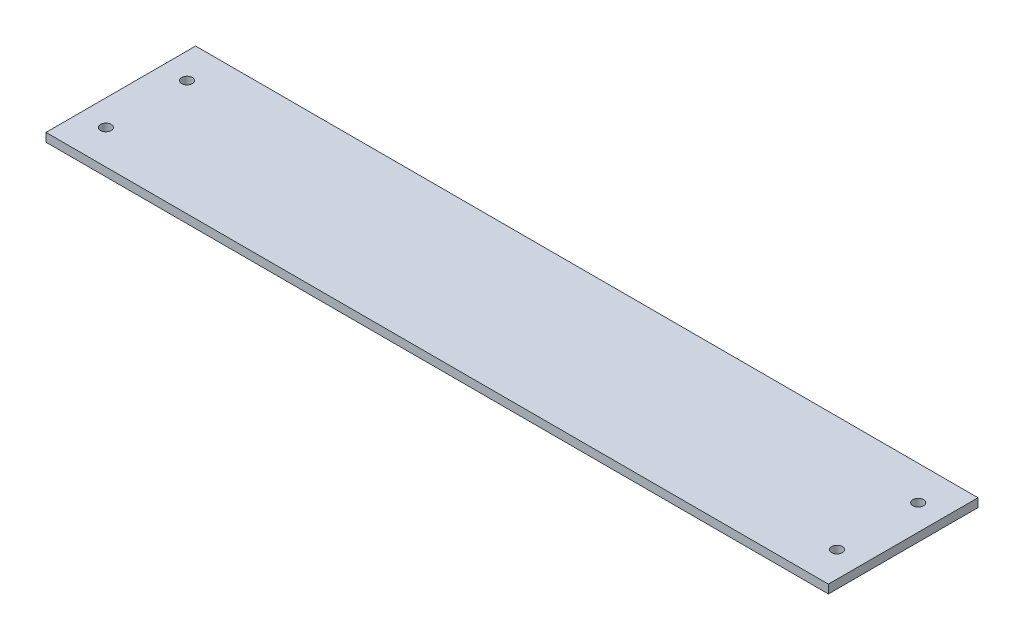
SolidWorks part; units mm, degrees
ref_plane "Front Plane" through (0, 0, 0) normal (0, 0, 1) x (1, 0, 0)
ref_plane "Top Plane" through (0, 0, 0) normal (0, 1, 0) x (1, 0, 0)
ref_plane "Right Plane" through (0, 0, 0) normal (1, 0, 0) x (0, 0, -1)
sketch "Sketch1" plane through (0, 0, 0) normal (0, 1, 0) x (1, 0, 0)
  line L1 (-91.52, 17.5) -> (91.52, 17.5)
  line L2 (-91.52, 17.5) -> (-91.52, -17.5)
  line L3 (-91.52, -17.5) -> (91.52, -17.5)
  line L4 (91.52, 17.5) -> (91.52, -17.5)
  line L5 (-91.52, 17.5) -> (91.52, -17.5) construction
  line L6 (-91.52, -17.5) -> (91.52, 17.5) construction
  point P0 (0, 0)
  dimension "D1" = 35
  dimension "D2" = 183.04
base flange "Base-Flange1" sketch "Sketch1" thickness 2 reverse thickness direction no parameters "D1"=2
hole_wizard "Tap Drill for M3 Tap1" positions "Sketch2" profile "Sketch3" hole size "M3" standard "AS" end condition through all
sketch "Sketch2" plane through (-65.8659, 2, 15.8304) normal (0, 1, 0) x (0, 0, -1)
  point P0 (25.3304, 19.6541)
  point P2 (6.3304, 19.6541)
  point P11 (0, 0)
sketch "Sketch3" plane through (-85.52, 2, -9.5) normal (1, 0, 0) x (0, 0, 1)
  line L0 (0, 0) -> (0, 4)
  line L1 (0, 4) -> (1.25, 4)
  line L2 (1.25, 4) -> (1.25, 0)
  line L3 (1.25, 0) -> (0, 0)
  line L4 (0, -6.35) -> (0, 107.95) construction
  dimension "Thru Hole Dia." = 2.5
  dimension "Thru Hole Depth" = 4
hole_wizard "Tap Drill for M3 Tap2" positions "Sketch4" profile "Sketch5" hole size "M3" standard "AS" end condition through all
sketch "Sketch4" plane through (-65.8659, 2, 15.8304) normal (0, 1, 0) x (0, 0, -1)
  point P0 (25.3304, -151.4044)
  point P2 (6.3304, -151.4044)
  point P11 (0, 0)
sketch "Sketch5" plane through (85.5385, 2, -9.5) normal (1, 0, 0) x (0, 0, 1)
  line L0 (0, 0) -> (0, 4)
  line L1 (0, 4) -> (1.25, 4)
  line L2 (1.25, 4) -> (1.25, 0)
  line L3 (1.25, 0) -> (0, 0)
  line L4 (0, -6.35) -> (0, 107.95) construction
  dimension "Thru Hole Dia." = 2.5
  dimension "Thru Hole Depth" = 4
sketch "Bend-Lines1" [suppressed] plane through (0, 0, 0) normal (0, 1, 0) x (1, 0, 0)
sketch "Bounding-Box1" [suppressed] plane through (0, 0, 0) normal (0, 1, 0) x (1, 0, 0)
sheet metal parameters "Sheet-Metal1" thickness 2 parameters "D1"=2
flat pattern "Flat-Pattern1" [suppressed]
sketch "Bend-Lines2" plane through (0, 0, 0) normal (0, 1, 0) x (1, 0, 0)
sketch3d "Bounding-Box2" [suppressed]
  line L0 (91.52, -17.5, 0) -> (-91.52, -17.5, 0) construction
  line L1 (91.52, 17.5, 0) -> (-91.52, 17.5, 0) construction
  line L2 (91.52, -17.5, 0) -> (91.52, 17.5, 0) construction
  line L3 (-91.52, -17.5, 0) -> (-91.52, 17.5, 0) construction
sheet metal parameters "Sheet-Metal2" thickness 2 parameters "D1"=2
flat pattern "Flat-Pattern1"
sketch "Bend-Lines2" plane through (0, 0, 0) normal (0, 1, 0) x (1, 0, 0)
sketch3d "Bounding-Box2" [suppressed]
  line L0 (91.52, -17.5, 0) -> (-91.52, -17.5, 0) construction
  line L1 (91.52, 17.5, 0) -> (-91.52, 17.5, 0) construction
  line L2 (91.52, -17.5, 0) -> (91.52, 17.5, 0) construction
  line L3 (-91.52, -17.5, 0) -> (-91.52, 17.5, 0) construction
sheet metal parameters "Sheet-Metal3" thickness 2 parameters "D1"=2
flat pattern "Flat-Pattern1"
sketch "Bend-Lines2" plane through (0, 0, 0) normal (0, 1, 0) x (1, 0, 0)
sketch3d "Bounding-Box2" [suppressed]
  line L0 (91.52, -17.5, 0) -> (-91.52, -17.5, 0) construction
  line L1 (91.52, 17.5, 0) -> (-91.52, 17.5, 0) construction
  line L2 (91.52, -17.5, 0) -> (91.52, 17.5, 0) construction
  line L3 (-91.52, -17.5, 0) -> (-91.52, 17.5, 0) construction
